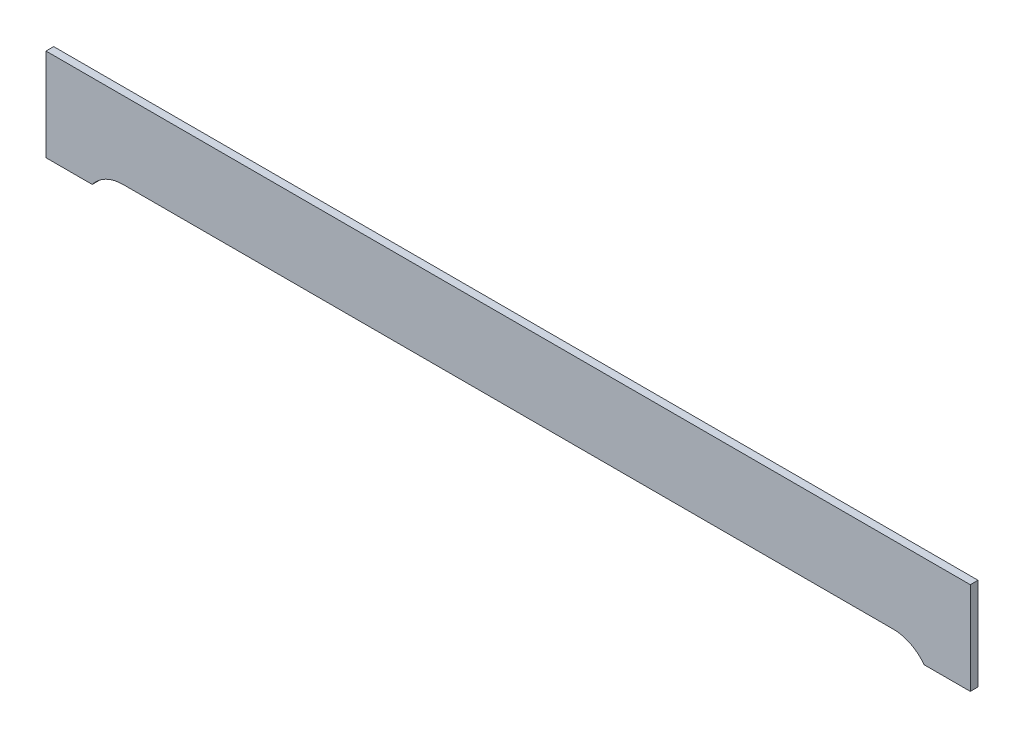
SolidWorks part; units mm, degrees
ref_plane "Front Plane" through (0, 0, 0) normal (0, 0, 1) x (1, 0, 0)
ref_plane "Top Plane" through (0, 0, 0) normal (0, 1, 0) x (1, 0, 0)
ref_plane "Right Plane" through (0, 0, 0) normal (1, 0, 0) x (0, 0, -1)
sketch "Sketch1" plane through (0, 0, 0) normal (0, 0, 1) x (1, 0, 0)
  line L0 (0, 0) -> (0, -10)
  line L1 (50, 0) -> (550, 0)
  line L2 (0, 0) -> (0, 50)
  line L3 (0, 50) -> (600, 50)
  line L4 (600, 0) -> (600, 50)
  line L5 (0, -10) -> (30, -10)
  line L6 (600, 0) -> (600, -10)
  line L7 (600, -10) -> (570, -10)
  arc A0 (30, -10) -> (50, 0) centre (50, -25) cw
  arc A1 (570, -10) -> (550, 0) centre (550, -25) ccw
  dimension "D7" = 25
  dimension "D8" = 25
  dimension "D1" = 600
  dimension "D2" = 50
  dimension "D3" = 10
  dimension "D4" = 10
  dimension "D5" = 30
  dimension "D6" = 30
  dimension "D9" = 10
  dimension "D10" = 10
extrude "Boss-Extrude1" add sketch "Sketch1" along normal blind 5
